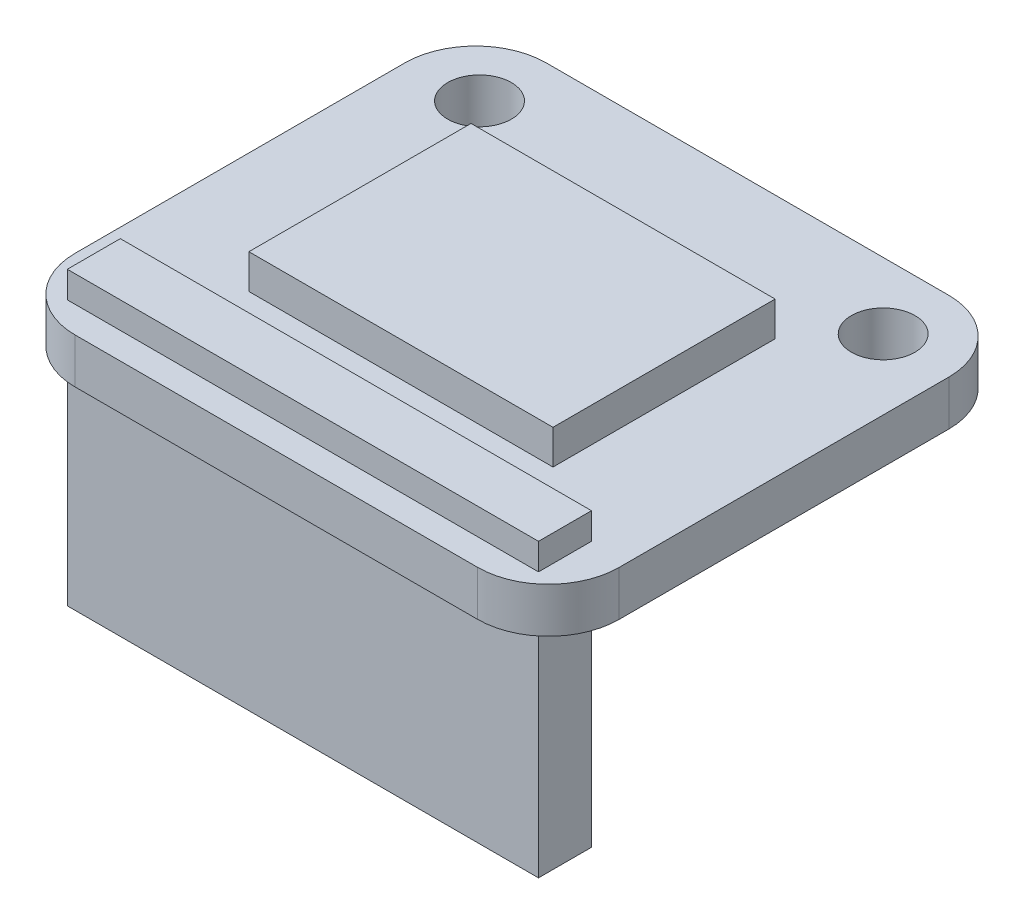
SolidWorks part; units mm, degrees
ref_plane "Front Plane" through (0, 0, 0) normal (0, 0, 1) x (1, 0, 0)
ref_plane "Top Plane" through (0, 0, 0) normal (0, 1, 0) x (1, 0, 0)
ref_plane "Right Plane" through (0, 0, 0) normal (1, 0, 0) x (0, 0, -1)
sketch "Sketch1" plane through (0, 0, 0) normal (0, 1, 0) x (1, 0, 0)
  line L1 (-7.595, -8.89) -> (7.595, -8.89)
  line L2 (-10.265, -6.22) -> (-10.265, 6.22)
  line L3 (-7.595, 8.89) -> (7.595, 8.89)
  line L4 (10.265, -6.22) -> (10.265, 6.22)
  line L5 (-10.265, -8.89) -> (10.265, 8.89) construction
  line L6 (-10.265, 8.89) -> (10.265, -8.89) construction
  arc A0 (-7.595, -8.89) -> (-10.265, -6.22) centre (-7.595, -6.22) cw
  arc A1 (7.595, -8.89) -> (10.265, -6.22) centre (7.595, -6.22) ccw
  arc A2 (7.595, 8.89) -> (10.265, 6.22) centre (7.595, 6.22) cw
  arc A3 (-10.265, 6.22) -> (-7.595, 8.89) centre (-7.595, 6.22) cw
  point P0 (0, 0)
  dimension "D3" = 2.67
  dimension "D1" = 17.78
  dimension "D2" = 20.53
extrude "Boss-Extrude1" add sketch "Sketch1" along normal blind 1.7
sketch "Sketch2" plane through (0, 1.7, 0) normal (0, 1, 0) x (1, 0, 0)
  line L1 (-5.7376, -4.191) -> (5.7376, -4.191)
  line L2 (-5.7376, -4.191) -> (-5.7376, 4.191)
  line L3 (-5.7376, 4.191) -> (5.7376, 4.191)
  line L4 (5.7376, -4.191) -> (5.7376, 4.191)
  line L5 (-5.7376, -4.191) -> (5.7376, 4.191) construction
  line L6 (-5.7376, 4.191) -> (5.7376, -4.191) construction
  point P0 (0, 0)
extrude "Boss-Extrude2" add sketch "Sketch2" along normal offset from surface (1.3 mm away) 3 up to face at (0, 0, 0)
sketch "Sketch3" plane through (0, 1.7, 0) normal (0, 1, 0) x (1, 0, 0)
  line L0 (-6.415, 6.39) -> (6.415, 6.39) construction
  line L1 (0, 8.89) -> (0, 6.39) construction
  line L2 (7.595, 8.89) -> (-7.595, 8.89) construction
  line L3 (-7.615, 7.59) -> (-7.615, 8.89) construction
  circle A0 centre (-7.615, 6.39) radius 1.2
  circle A1 centre (7.615, 6.39) radius 1.2
  dimension "D1" = 2.4
  dimension "D2" = 12.83
  dimension "D3" = 1.3
extrude "Cut-Extrude1" cut sketch "Sketch3" against normal through all
sketch "Sketch4" plane through (0, 1.7, 0) normal (0, 1, 0) x (1, 0, 0)
  line L0 (0, -5.89) -> (0, 0) construction
  line L1 (-8.89, -5.89) -> (8.89, -5.89)
  line L2 (-8.89, -5.89) -> (-8.89, -7.89)
  line L3 (-8.89, -7.89) -> (8.89, -7.89)
  line L4 (8.89, -5.89) -> (8.89, -7.89)
  line L5 (-7.595, -8.89) -> (7.595, -8.89) construction
  dimension "D1" = 2
  dimension "D2" = 17.78
  dimension "D3" = 1
extrude "Boss-Extrude3" add sketch "Sketch4" along normal blind 1 and the other way blind 10
